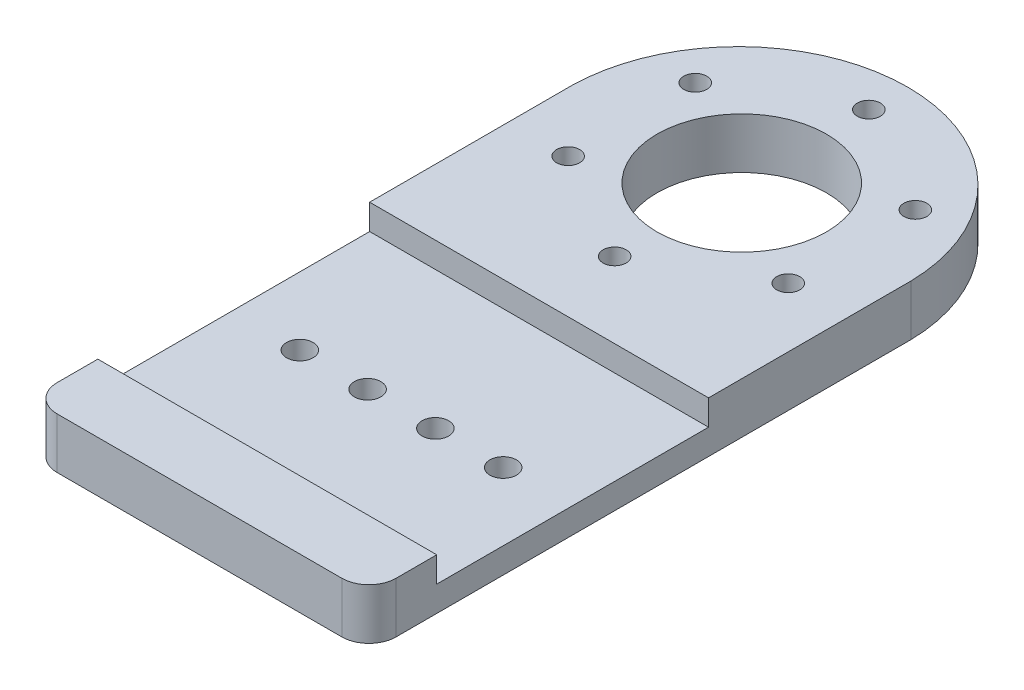
SolidWorks part; units mm, degrees
ref_plane "Front Plane" through (0, 0, 0) normal (0, 0, 1) x (1, 0, 0)
ref_plane "Top Plane" through (0, 0, 0) normal (0, 1, 0) x (1, 0, 0)
ref_plane "Right Plane" through (0, 0, 0) normal (1, 0, 0) x (0, 0, -1)
sketch "Sketch1" plane through (0, 0, 0) normal (0, 1, 0) x (1, 0, 0)
  line L0 (0, -111.3091) -> (63.5, -111.3091)
  line L2 (0, -22.4091) -> (0, -124.0091)
  line L3 (0, -124.0091) -> (63.5, -124.0091)
  line L4 (63.5, -22.4091) -> (63.5, -124.0091)
  line L5 (0, -9.7091) -> (50000, -9.7091) construction
  line L6 (31.75, -22.4091) -> (-49968.25, -22.4091) construction
  line L7 (0, -60.3821) -> (63.5, -60.3821)
  circle A0 centre (31.75, -22.4091) radius 15.875
  circle A1 centre (12.7, -86.1631) radius 2.4892
  circle A2 centre (25.4, -86.1631) radius 2.4892
  circle A3 centre (38.1, -86.1631) radius 2.4892
  circle A4 centre (50.8, -86.1631) radius 2.4892
  arc A8 (63.5, -22.4091) -> (0, -22.4091) centre (31.75, -23.0483) ccw
  point P25 (63.5, -9.7091)
  dimension "D3" = 31.75
  dimension "D5" = 31.75
  dimension "D6" = 4.9784
  dimension "D7" = 12.7
  dimension "D8" = 37.846
  dimension "D10" = 12.7
  dimension "D12" = 63.627
  dimension "D9" = 4
extrude "Boss-Extrude2" add sketch "Sketch1" along normal blind 9.525 contours L4 L0 L2 L3 | L2 L7 L4 A0 | L5 A0 region at (31.75, 0, 117.6591) region at (0.9384, 0, 41.3956)
extrude "Boss-Extrude3" add sketch "Sketch1<3>" along normal blind 4.7625 contours L7 L2 L0 L4 A4 A3 A2 A1 region at (31.75, 0, 85.8377)
sketch "Sketch1<3>" plane through (0, 0, 0) normal (0, 1, 0) x (1, 0, 0) same geometry as "Sketch1"
sketch "Sketch2" plane through (0, 0, 0) normal (0, -1, 0) x (1, 0, 0)
  line L0 (31.75, 22.4091) -> (11.1278, 34.3153) construction
  line L1 (31.75, 22.4091) -> (31.75, 46.2216) construction
  circle A0 centre (11.1278, 34.3153) radius 2.159
  circle A4 centre (31.75, 22.4091) radius 23.8125 construction
  circle A5 centre (31.75, 46.2216) radius 2.159
  circle A6 centre (52.3722, 34.3153) radius 2.159
  circle A7 centre (52.3722, 10.5028) radius 2.159
  circle A8 centre (31.75, -1.4034) radius 2.159
  circle A9 centre (11.1278, 10.5028) radius 2.159
  dimension "D1" = 4.318
  dimension "D3" = 60
  dimension "D4" = 47.625
  dimension "D2" = 6
extrude "Cut-Extrude1" cut sketch "Sketch2" against normal through all
sketch "Sketch3" plane through (0, 0, 0) normal (0, -1, 0) x (1, 0, 0)
  line L0 (-939.958, 124.0091) -> (49060.042, 124.0091) construction
  line L2 (63.5, -875.9909) -> (63.5, 49124.0091) construction
  point P3 (63.5, 124.0091)
fillet "Fillet1" radius 5.08 2 edges at (0, 4.7625, 124.0091) (63.5, 4.7625, 124.0091)
